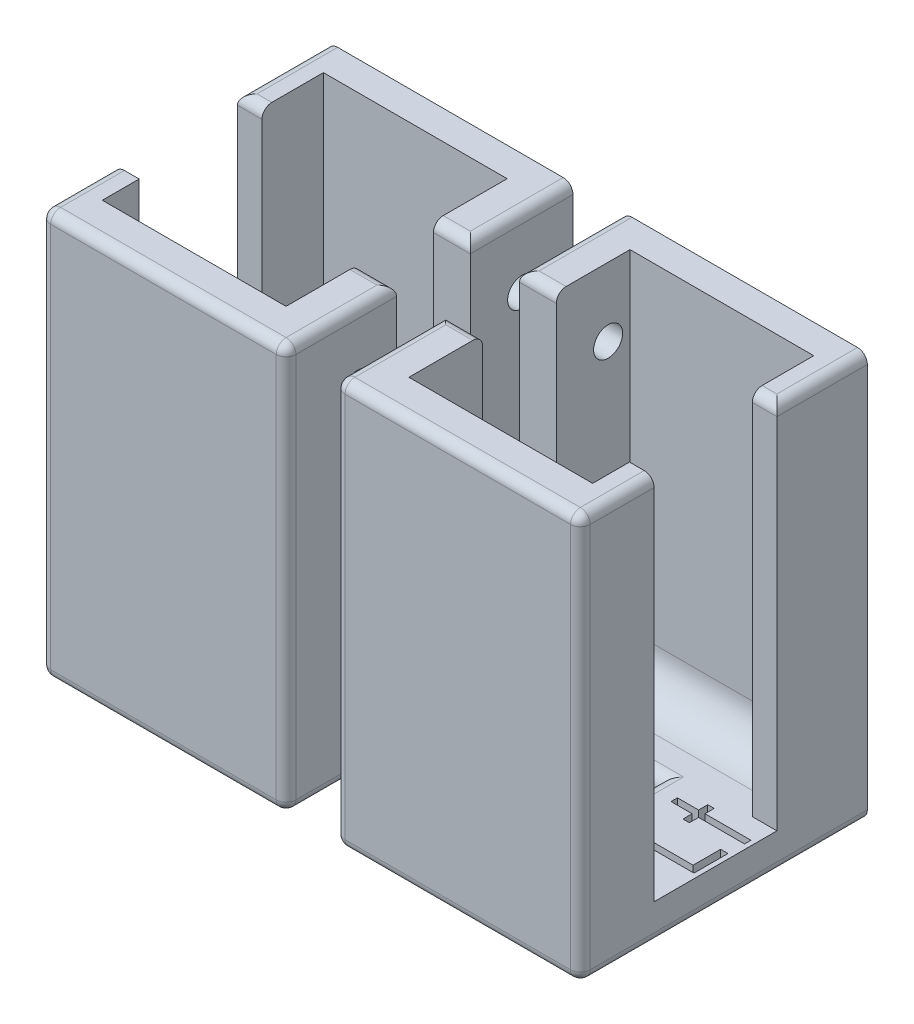
SolidWorks part; units mm, degrees
ref_plane "Front Plane" through (0, 0, 0) normal (0, 0, 1) x (1, 0, 0)
ref_plane "Top Plane" through (0, 0, 0) normal (0, 1, 0) x (1, 0, 0)
ref_plane "Right Plane" through (0, 0, 0) normal (1, 0, 0) x (0, 0, -1)
sketch "Sketch2" plane through (0, 0, 0) normal (0, 1, 0) x (1, 0, 0)
  line L0 (-9.5, -11.43) -> (9.5, -11.43)
  line L5 (12.04, -14.43) -> (-13.31, -14.43)
  line L10 (-13.31, -14.43) -> (-13.31, 15.24)
  line L15 (-13.31, 15.24) -> (12.04, 15.24)
  line L16 (12.04, 15.24) -> (12.04, 7.62)
  line L17 (12.04, -14.43) -> (12.04, -5.08)
  line L18 (12.04, 7.62) -> (9.5, 7.62)
  line L19 (9.5, 7.62) -> (9.5, 11.43)
  line L20 (9.5, 11.43) -> (-9.5, 11.43)
  line L21 (-9.5, 11.43) -> (-9.5, -11.43)
  line L22 (12.04, -5.08) -> (9.5, -5.08)
  line L24 (9.5, -11.43) -> (9.5, -5.08)
  point P6 (0, 11.43)
  point P12 (-9.5, 0)
  dimension "D1" = 22.86
  dimension "D2" = 19
  dimension "D3" = 3.81
  dimension "D4" = 3.81
  dimension "D5" = 7.62
  dimension "D6" = 2.54
  dimension "D7" = 5.08
  dimension "D8" = 3
extrude "Boss-Extrude2" add sketch "Sketch2" along normal blind 38.1
sketch "Sketch1" plane through (0, 0, 0) normal (0, 1, 0) x (1, 0, 0)
  line L1 (-13.31, -14.43) -> (12.04, -14.43)
  line L2 (-13.31, -14.43) -> (-13.31, 15.24)
  line L3 (-13.31, 15.24) -> (12.04, 15.24)
  line L4 (12.04, -14.43) -> (12.04, 15.24)
  point P0 (0, 0)
extrude "Boss-Extrude3" add sketch "Sketch1" against normal blind 3.81
sketch "Sketch3" plane through (0, 0, 0) normal (0, 1, 0) x (1, 0, 0)
  line L1 (-1.88, -3.81) -> (1.12, -3.81)
  line L2 (-1.88, -3.81) -> (-1.88, 3.81)
  line L3 (-1.88, 3.81) -> (1.12, 3.81)
  line L4 (1.12, -3.81) -> (1.12, 3.81)
  line L5 (-9.5, -11.43) -> (-9.5, 11.43) construction
  point P6 (-1.88, 0)
  dimension "D1" = 7.62
  dimension "D2" = 3
  dimension "D3" = 7.62
extrude "Cut-Extrude1" cut sketch "Sketch3" against normal through all
sketch "Sketch4" plane through (-9.5, 0, 0) normal (1, 0, 0) x (0, 0, -1)
  line L0 (-11.43, 38.1) -> (11.43, 38.1) construction
  line L1 (-3.81, 38.1) -> (3.81, 38.1)
  line L2 (-3.81, 38.1) -> (-3.81, 8)
  line L3 (-3.81, 8) -> (3.81, 8)
  line L4 (3.81, 38.1) -> (3.81, 8)
  line L5 (-11.43, 0) -> (11.43, 0) construction
  line L6 (-11.43, 38.1) -> (11.43, 38.1) construction
  point P10 (0, 38.1)
  point P11 (0, 38.1)
  dimension "D1" = 8
  dimension "D2" = 7.62
extrude "Cut-Extrude2" cut sketch "Sketch4" against normal through all
sketch "Sketch5" plane through (-9.5, 0, 0) normal (1, 0, 0) x (0, 0, -1)
  line L1 (-11.43, 0) -> (11.43, 0) construction
  circle A0 centre (-9.17, 31) radius 1.5
  circle A1 centre (7.848, 31) radius 1.5
  dimension "D3" = 3
  dimension "D1" = 2.26
  dimension "D2" = 17.018
  dimension "D4" = 31
extrude "Cut-Extrude3" cut sketch "Sketch5" against normal through all
sketch "Sketch6" plane through (0, 0, 14.43) normal (0, 0, 1) x (1, 0, 0)
  line L0 (-13.31, 38.1) -> (-13.31, -3.81) construction
  line L3 (-1.88, -3.81) -> (-1.88, 0) construction
  line L8 (12.04, 38.1) -> (12.04, 0) construction
  line L11 (-13.31, 38.1) -> (-9.5, 38.1) construction
  circle A0 centre (-11.405, 19.05) radius 1.45
  circle A1 centre (-3.81, -1.905) radius 1.45
  point P9 (-1.88, -1.905)
  point P20 (-11.405, 38.1)
  point P26 (12.04, 19.05)
  dimension "D1" = 2.9
  dimension "D2" = 9.5
extrude "Cut-Extrude4" cut sketch "Sketch6" against normal offset from surface (24.844 mm away) 6.604 up to face at (-11.405, 23.05, -3.81) offset beyond the face yes
fillet "Fillet1" radius 4 2 edges at (0, 0, -11.43) (0, 0, 11.43)
mirror "Mirror1" about plane through (0, 0, 0) normal (0, 0, 1) of bodies 106 120
delete or keep bodies "Body-Delete/Keep 1" type keep bodies bodies 116
fillet "Fillet4" radius 2.54 2 edges at (-11.405, 8, -3.81) (-11.405, 8, 3.81)
fillet "Fillet2" radius 1.016 11 edges at (-0.635, -3.81, 15.24) (-13.31, 17.145, 15.24) (-0.635, 38.1, 15.24) (12.04, 17.145, 15.24) (-13.31, -3.81, 0.405) (12.04, -3.81, 0.405) (12.04, 38.1, 11.43) (-13.31, 38.1, 9.525) (-13.31, 38.1, -9.12) (-11.405, 38.1, -3.81) (-11.405, 38.1, 3.81)
fillet "Fillet3" radius 1.27 4 edges at (-0.38, 0, -3.81) (-1.88, 0, 0) (-0.38, 0, 3.81) (1.12, 0, 0)
fillet "Fillet5" radius 1.016 2 edges at (10.77, 38.1, -5.08) (12.04, 38.1, -9.755)
ref_plane "Plane1" through (-15.85, 0, 0) normal (-1, 0, 0) x (0, 0, 1)
mirror "Mirror3" about plane through (-15.85, 0, 0) normal (-1, 0, 0) of bodies 116 117 121
sketch "Sketch7" plane through (0, 0, 0) normal (0, 1, 0) x (1, 0, 0)
  line L0 (11.5383, -3.9427) -> (11.5383, 17.9144) construction
  text T0 "Lt\r\n" font "Century Gothic" height in points 28
extrude "Cut-Extrude5" cut sketch "Sketch7" against normal blind 1.27
sketch "Sketch8" plane through (0, 0, 0) normal (0, 1, 0) x (1, 0, 0)
  line L0 (-42.724, -6.0799) -> (-42.724, 4.0801) construction
  line L1 (-42.724, -14.224) -> (-42.724, -7.62) construction
  text T0 "Rt\r\n" font "Century Gothic" height in points 28
  dimension "D1" = 10.16
extrude "Cut-Extrude6" cut sketch "Sketch8" against normal blind 1.27
equation "\".30.83in\"=0.83"
